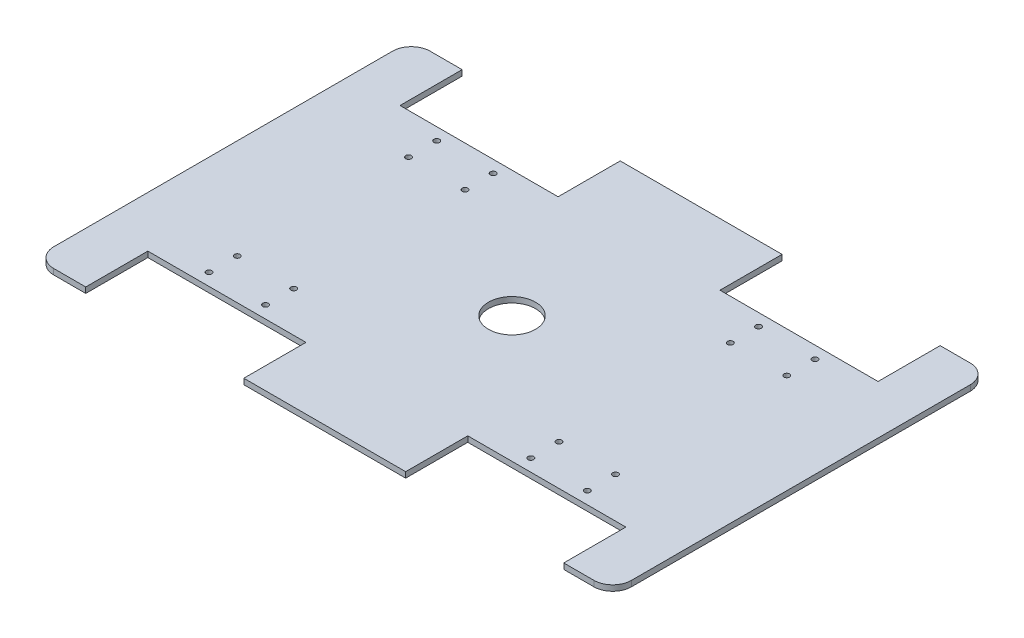
SolidWorks part; units mm, degrees
ref_plane "前视基准面" through (0, 0, 0) normal (0, 0, 1) x (1, 0, 0)
ref_plane "上视基准面" through (0, 0, 0) normal (0, 1, 0) x (1, 0, 0)
ref_plane "右视基准面" through (0, 0, 0) normal (1, 0, 0) x (0, 0, -1)
other "Configuration Table"
sketch "草图1" plane through (0, 0, 0) normal (0, 1, 0) x (1, 0, 0)
  line L1 (-197.4956, -53.965) -> (109.5044, -53.965)
  line L2 (-197.4956, -53.965) -> (-197.4956, 146.035)
  line L3 (-197.4956, 146.035) -> (109.5044, 146.035)
  line L4 (109.5044, -53.965) -> (109.5044, 146.035)
  line L5 (-197.4956, -53.965) -> (109.5044, 146.035) construction
  line L6 (-197.4956, 146.035) -> (109.5044, -53.965) construction
  point P0 (-43.9956, 46.035)
  dimension "D1" = 200
  dimension "D2" = 307
extrude "凸台-拉伸1" add sketch "草图1" along normal blind 3
sketch "草图2" plane through (0, 3, 0) normal (0, 1, 0) x (1, 0, 0)
  line L0 (109.5044, 146.035) -> (-197.4956, 146.035) construction
  line L1 (-170.4956, 146.035) -> (-86.4956, 146.035)
  line L2 (-170.4956, 146.035) -> (-170.4956, 113.035)
  line L3 (-170.4956, 113.035) -> (-86.4956, 113.035)
  line L4 (-86.4956, 146.035) -> (-86.4956, 113.035)
  line L5 (-197.4956, 146.035) -> (-197.4956, -53.965) construction
  dimension "D1" = 27
  dimension "D2" = 84
  dimension "D3" = 33
extrude "切除-拉伸1" cut sketch "草图2" against normal blind 3
sketch "草图3" plane through (0, 3, 0) normal (0, 1, 0) x (1, 0, 0)
  line L3 (9.5044, -47.3376) -> (9.5044, 78.455) construction
  line L4 (-197.4956, 46.035) -> (109.5044, 46.035) construction
  line L5 (-197.4956, 146.035) -> (-197.4956, -53.965) construction
  line L6 (109.5044, -53.965) -> (109.5044, 146.035) construction
pattern_linear "阵列(线性)1" count 2 spacing 170 along (1, 0, 0) count 2 spacing 167 along (0, 0, 1) of "切除-拉伸1"
ref_plane "基准面1" through (-197.4956, 3, -146.035) normal (-1, 0, 0) x (0, 0, 1)
ref_plane "基准面2" through (-197.4956, 3, 53.965) normal (1, 0, 0) x (0, 0, -1)
sketch "草图6" plane through (0, 3, 0) normal (0, 1, 0) x (1, 0, 0)
  line L0 (-197.4956, 46.035) -> (109.5044, 46.035) construction
  circle A0 centre (-43.9956, 46.035) radius 12.5
  dimension "D1" = 25
extrude "切除-拉伸2" cut sketch "草图6" against normal blind 3
fillet "圆角1" radius 10 4 edges at (-197.4956, 1.5, -146.035) (-197.4956, 1.5, 53.965) (109.5044, 1.5, 53.965) (109.5044, 1.5, -146.035)
sketch "草图11" plane through (0, 0, 0) normal (0, -1, 0) x (1, 0, 0)
  line L0 (22.3374, 6.965) -> (60.2893, 6.965) construction
  line L1 (41.5044, -5.1386) -> (41.5044, 18.3273) construction
  circle A0 centre (26.5044, 14.465) radius 1.5
  circle A1 centre (56.5044, 14.465) radius 1.5
  circle A2 centre (56.5044, -0.535) radius 1.5
  circle A3 centre (26.5044, -0.535) radius 1.5
extrude "切除-拉伸3" cut sketch "草图11" against normal blind 10 contours A0 | A1
extrude "切除-拉伸4" cut sketch "草图11<3>" against normal blind 10
sketch "草图11<3>" plane through (0, 0, 0) normal (0, -1, 0) x (1, 0, 0) same geometry as "草图11"
ref_plane "基准面3" through (0, 0, -46.035) normal (0, 0, -1) x (-1, 0, 0)
ref_plane "基准面4" through (-43.9956, 0, 0) normal (1, 0, 0) x (0, 0, -1)
mirror "镜向2" about plane through (-43.9956, 0, 0) normal (1, 0, 0) of "切除-拉伸3", "切除-拉伸4" second plane through (0, 0, -46.035) second plane normal (0, 0, -1)
